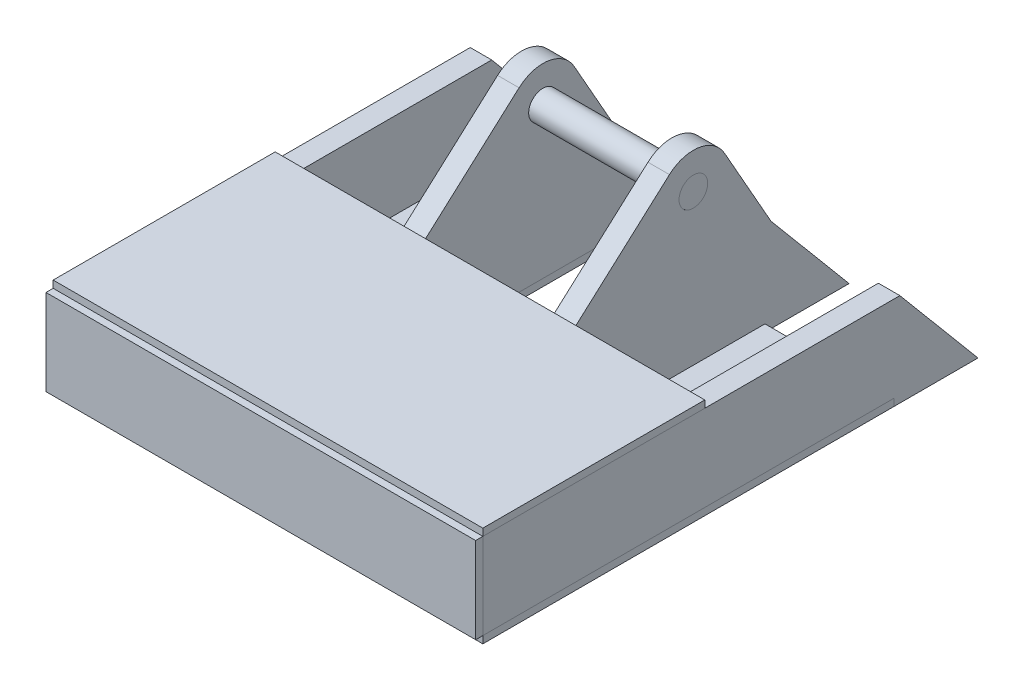
SolidWorks part; units mm, degrees
material "Alum Plate"
ref_plane "Front Plane" through (0, 0, 0) normal (0, 0, 1) x (1, 0, 0)
ref_plane "Top Plane" through (0, 0, 0) normal (0, 1, 0) x (1, 0, 0)
ref_plane "Right Plane" through (0, 0, 0) normal (1, 0, 0) x (0, 0, -1)
other "Bounding Box"
ref_plane "Default Plane" through (-8.9266, -12.7485, 0) normal (-0.1736, 0.9848, 0) x (0.9848, 0.1736, 0)
sketch "Sketch1" plane through (0, 0, 0) normal (0, 1, 0) x (1, 0, 0)
  line L0 (0, 0) -> (95.25, 0) construction
  line L1 (0, 0) -> (-95.25, 0) construction
  line L2 (-95.25, 139.7) -> (-146.05, 139.7) construction
  line L3 (95.25, 139.7) -> (146.05, 139.7) construction
  line L4 (0, 139.7) -> (0, 0) construction
  line L5 (-28.575, 131.445) -> (0, 131.445) construction
  line L6 (-95.25, 163.195) -> (95.25, 163.195) construction
  line L7 (-95.25, 163.195) -> (-95.25, -19.05) construction
  line L8 (-95.25, -19.05) -> (95.25, -19.05) construction
  line L9 (95.25, 163.195) -> (95.25, -19.05) construction
  line L10 (-78.105, 121.725) -> (-38.1, 121.725)
  line L11 (-78.105, 121.725) -> (-78.105, 157.725)
  line L12 (-78.105, 157.725) -> (-38.1, 157.725)
  line L13 (-38.1, 121.725) -> (-38.1, 157.725)
  line L14 (-78.105, 121.725) -> (-38.1, 157.725) construction
  line L15 (-78.105, 157.725) -> (-38.1, 121.725) construction
  line L16 (-78.105, 82.55) -> (-38.1, 82.55)
  line L17 (-78.105, 82.55) -> (-78.105, 118.55)
  line L18 (-78.105, 118.55) -> (-38.1, 118.55)
  line L19 (-38.1, 82.55) -> (-38.1, 118.55)
  line L20 (-78.105, 82.55) -> (-38.1, 118.55) construction
  line L21 (-78.105, 118.55) -> (-38.1, 82.55) construction
  line L22 (-38.1, 82.55) -> (-3.175, 82.55)
  line L23 (-38.1, 82.55) -> (-38.1, 118.55)
  line L24 (-38.1, 118.55) -> (-3.175, 118.55)
  line L25 (-3.175, 82.55) -> (-3.175, 118.55)
  line L26 (-38.1, 82.55) -> (-3.175, 118.55) construction
  line L27 (-38.1, 118.55) -> (-3.175, 82.55) construction
  line L28 (-28.575, 163.195) -> (-38.1, 163.195)
  line L29 (-28.575, 163.195) -> (-28.575, 79.375)
  line L30 (-28.575, 79.375) -> (-38.1, 79.375)
  line L31 (-38.1, 163.195) -> (-38.1, 79.375)
  line L32 (-28.575, 163.195) -> (-38.1, 79.375) construction
  line L33 (-28.575, 79.375) -> (-38.1, 163.195) construction
  line L34 (28.575, 163.195) -> (38.1, 163.195)
  line L35 (28.575, 163.195) -> (28.575, 79.375)
  line L36 (28.575, 79.375) -> (38.1, 79.375)
  line L37 (38.1, 163.195) -> (38.1, 79.375)
  line L38 (28.575, 163.195) -> (38.1, 79.375) construction
  line L39 (28.575, 79.375) -> (38.1, 163.195) construction
  line L40 (-95.25, 79.375) -> (95.25, 79.375)
  line L41 (-95.25, 79.375) -> (-95.25, 69.85)
  line L42 (-95.25, 69.85) -> (95.25, 69.85)
  line L43 (95.25, 79.375) -> (95.25, 69.85)
  line L44 (-95.25, 79.375) -> (95.25, 69.85) construction
  line L45 (-95.25, 69.85) -> (95.25, 79.375) construction
  line L46 (95.25, -19.05) -> (85.725, -19.05)
  line L47 (95.25, -19.05) -> (95.25, 163.195)
  line L48 (95.25, 163.195) -> (85.725, 163.195)
  line L49 (85.725, -19.05) -> (85.725, 163.195)
  line L50 (95.25, -19.05) -> (85.725, 163.195) construction
  line L51 (95.25, 163.195) -> (85.725, -19.05) construction
  line L52 (-95.25, -19.05) -> (-85.725, -19.05)
  line L53 (-95.25, -19.05) -> (-95.25, 163.195)
  line L54 (-95.25, 163.195) -> (-85.725, 163.195)
  line L55 (-85.725, -19.05) -> (-85.725, 163.195)
  line L56 (-95.25, -19.05) -> (-85.725, 163.195) construction
  line L57 (-95.25, 163.195) -> (-85.725, -19.05) construction
  line L58 (0, 131.445) -> (28.575, 131.445) construction
  line L59 (-95.25, 0) -> (-146.05, 0) construction
  line L60 (40.64, 82.55) -> (83.185, 82.55)
  line L61 (40.64, 82.55) -> (40.64, 160.02)
  line L62 (40.64, 160.02) -> (83.185, 160.02)
  line L63 (83.185, 82.55) -> (83.185, 160.02)
  line L64 (40.64, 82.55) -> (83.185, 160.02) construction
  line L65 (40.64, 160.02) -> (83.185, 82.55) construction
  line L66 (-95.25, -19.05) -> (95.25, -19.05)
  line L67 (-95.25, -19.05) -> (-95.25, -22.225)
  line L68 (-95.25, -22.225) -> (95.25, -22.225)
  line L69 (95.25, -19.05) -> (95.25, -22.225)
  line L70 (-95.25, -19.05) -> (95.25, -22.225) construction
  line L71 (-95.25, -22.225) -> (95.25, -19.05) construction
  line L72 (-85.725, -19.05) -> (-43.815, -19.05)
  line L73 (-85.725, -19.05) -> (-85.725, 19.05)
  line L74 (-85.725, 19.05) -> (-43.815, 19.05)
  line L75 (-43.815, -19.05) -> (-43.815, 19.05)
  line L76 (-85.725, -19.05) -> (-43.815, 19.05) construction
  line L77 (-85.725, 19.05) -> (-43.815, -19.05) construction
  line L78 (43.815, 19.05) -> (85.725, 19.05)
  line L79 (43.815, 19.05) -> (43.815, -19.05)
  line L80 (43.815, -19.05) -> (85.725, -19.05)
  line L81 (85.725, 19.05) -> (85.725, -19.05)
  line L82 (43.815, 19.05) -> (85.725, -19.05) construction
  line L83 (43.815, -19.05) -> (85.725, 19.05) construction
  line L84 (95.25, 0) -> (146.05, 0) construction
  line L85 (40.64, 121.285) -> (38.1, 121.285) construction
  line L86 (83.185, 121.285) -> (85.725, 121.285) construction
  line L88 (-8.89, -18) -> (-43.815, -18)
  line L89 (-8.89, -18) -> (-8.89, 18)
  line L90 (-8.89, 18) -> (-43.815, 18)
  line L91 (-43.815, -18) -> (-43.815, 18)
  line L92 (-8.89, -18) -> (-43.815, 18) construction
  line L93 (-8.89, 18) -> (-43.815, -18) construction
  line L94 (8.89, -18) -> (43.815, -18)
  line L95 (8.89, -18) -> (8.89, 18)
  line L96 (8.89, 18) -> (43.815, 18)
  line L97 (43.815, -18) -> (43.815, 18)
  line L98 (8.89, -18) -> (43.815, 18) construction
  line L99 (8.89, 18) -> (43.815, -18) construction
  point P15 (-58.1025, 100.55)
  point P23 (-58.1025, 139.725)
  point P26 (-20.6375, 100.55)
  point P30 (33.3375, 121.285)
  point P37 (-33.3375, 121.285)
  point P40 (0, 74.6125)
  point P43 (90.4875, 72.0725)
  point P46 (-90.4875, 72.0725)
  point P52 (0, -20.6375)
  point P54 (61.9125, 121.285)
  point P60 (64.77, 0)
  point P62 (-64.77, 0)
  point P71 (-26.3525, 0)
  point P78 (26.3525, 0)
  dimension "D1" = 36
  dimension "D2" = 47.625
  dimension "D3" = 3.175
  dimension "D4" = 34.925
  dimension "D5" = 40.005
  dimension "D6" = 38.1
  dimension "D7" = 9.525
  dimension "D8" = 9.525
  dimension "D9" = 42.545
  dimension "D10" = 77.47
  dimension "D11" = 3.175
  dimension "D12" = 3.175
  dimension "D13" = 3.175
  dimension "D14" = 38.1
  dimension "D15" = 41.91
  dimension "D16" = 139.7
  dimension "D17" = 3.175
  dimension "D18" = 50.8
  dimension "D19" = 88.9
  dimension "D20" = 9.525
  dimension "D21" = 36
  dimension "D22" = 34.925
  dimension "D23" = 31.75
sketch "Sketch2" plane through (0, 0, 0) normal (1, 0, 0) x (0, 0, -1)
  line L0 (-277.7757, 0) -> (556.0914, 0) construction
  line L1 (0, 31.75) -> (0, 0) construction
  line L2 (139.7, 0) -> (139.7, 31.75) construction
  line L3 (-19.05, 31.75) -> (0, 31.75) construction
  line L4 (-19.05, 12.7) -> (163.195, 12.7)
  line L5 (-19.05, 12.7) -> (-19.05, 50.8)
  line L6 (-19.05, 50.8) -> (163.195, 50.8)
  line L7 (163.195, 12.7) -> (163.195, 50.8)
  line L8 (-19.05, 12.7) -> (163.195, 50.8) construction
  line L9 (-19.05, 50.8) -> (163.195, 12.7) construction
  line L10 (0, 31.75) -> (139.7, 31.75) construction
  line L11 (139.7, 31.75) -> (163.195, 31.75) construction
  line L12 (131.445, 79.375) -> (131.445, 0) construction
  line L13 (-19.05, 12.7) -> (-22.225, 12.7)
  line L14 (-19.05, 12.7) -> (-19.05, 50.8)
  line L15 (-19.05, 50.8) -> (-22.225, 50.8)
  line L16 (-22.225, 12.7) -> (-22.225, 50.8)
  line L17 (-19.05, 12.7) -> (-22.225, 50.8) construction
  line L18 (-19.05, 50.8) -> (-22.225, 12.7) construction
  line L19 (79.375, 50.8) -> (69.85, 50.8)
  line L20 (79.375, 50.8) -> (79.375, 12.7)
  line L21 (79.375, 12.7) -> (69.85, 12.7)
  line L22 (69.85, 50.8) -> (69.85, 12.7)
  line L23 (79.375, 50.8) -> (69.85, 12.7) construction
  line L24 (79.375, 12.7) -> (69.85, 50.8) construction
  line L25 (-90.4552, 66.9109) -> (131.445, 79.375) construction
  line L26 (-22.225, 12.7) -> (163.195, 12.7)
  line L27 (-22.225, 12.7) -> (-22.225, 9.525)
  line L28 (-22.225, 9.525) -> (163.195, 9.525)
  line L29 (163.195, 12.7) -> (163.195, 9.525)
  line L30 (-22.225, 12.7) -> (163.195, 9.525) construction
  line L31 (-22.225, 9.525) -> (163.195, 12.7) construction
  line L32 (-22.225, 50.8) -> (163.195, 50.8)
  line L33 (-22.225, 50.8) -> (-22.225, 53.975)
  line L34 (-22.225, 53.975) -> (163.195, 53.975)
  line L35 (163.195, 50.8) -> (163.195, 53.975)
  line L36 (-22.225, 50.8) -> (163.195, 53.975) construction
  line L37 (-22.225, 53.975) -> (163.195, 50.8) construction
  line L40 (-90.7074, 85.9592) -> (131.3189, 88.8992)
  line L41 (132.3863, 69.8966) -> (-88.5727, 47.9542)
  line L42 (100.55, 39.0496) -> (131.445, 79.375) construction
  line L43 (131.445, 79.375) -> (139.725, 29.2543) construction
  line L45 (163.195, 53.975) -> (200.493, 9.525)
  line L46 (200.493, 9.525) -> (163.195, 9.525)
  circle A0 centre (0, 31.75) radius 31.75
  circle A2 centre (100.55, 39.0496) radius 18
  circle A3 centre (139.725, 29.2543) radius 18
  circle A4 centre (131.445, 79.375) radius 23.8125
  circle A5 centre (139.725, 29.2543) radius 12.7
  circle A6 centre (100.55, 39.0496) radius 9.525
  circle A7 centre (139.7, 25.4) radius 25.4
  circle A8 centre (-90.4552, 66.9109) radius 63.5
  circle A11 centre (-90.4552, 66.9109) radius 19.05
  circle A12 centre (131.445, 79.375) radius 9.525
  point P13 (-20.6375, 31.75)
  point P15 (72.0725, 31.75)
  point P21 (74.6125, 31.75)
  point P34 (82.55, 39.0496)
  point P35 (118.55, 39.0496)
  point P36 (121.725, 29.2543)
  point P37 (157.725, 29.2543)
  point P52 (70.485, 11.1125)
  point P54 (70.485, 52.3875)
  dimension "D1" = 63.5
  dimension "D3" = 19.05
  dimension "D4" = 25.4
  dimension "D5" = 47.625
  dimension "D8" = 50.8
  dimension "D9" = 127
  dimension "D10" = 38.1
  dimension "D2" = 38.1
  dimension "D6" = 3.175
  dimension "D7" = 3.175
  dimension "D11" = 222.25
  dimension "D12" = 25.4
  dimension "D13" = 50.8
  dimension "D14" = 50.8
  dimension "D15" = 50
sketch "Sketch3" plane through (0, 0, 0) normal (1, 0, 0) x (0, 0, -1)
  line L1 (69.85, 50.8) -> (79.375, 50.8)
  line L2 (69.85, 50.8) -> (69.85, 12.7)
  line L3 (69.85, 12.7) -> (79.375, 12.7)
  line L4 (79.375, 50.8) -> (79.375, 12.7)
  line L5 (69.85, 50.8) -> (79.375, 12.7) construction
  line L6 (69.85, 12.7) -> (79.375, 50.8) construction
  point P0 (74.6125, 31.75)
extrude "Boss-Extrude1" add sketch "Sketch3" along normal up to vertex (85.725 mm away) and the other way up to vertex (85.725 mm away) up to point (85.725, 0, 19.05) other way up to point (-85.725, 0, 19.05)
sketch "Sketch4" plane through (-85.725, 0, 0) normal (-1, 0, 0) x (0, 0, 1)
  line L0 (-200.493, 9.525) -> (-165.8591, 50.8)
  line L2 (-165.8591, 50.8) -> (19.05, 50.8)
  line L3 (19.05, 50.8) -> (19.05, 12.7)
  line L4 (19.05, 12.7) -> (-163.195, 12.7)
  line L5 (-163.195, 12.7) -> (-163.195, 9.525)
  line L6 (22.225, 12.7) -> (-163.195, 9.525) construction
  line L7 (22.225, 9.525) -> (-163.195, 9.525) construction
  line L8 (-163.195, 9.525) -> (-200.493, 9.525)
  line L10 (-163.195, 53.975) -> (-200.493, 9.525) construction
  point P4 (-165.8591, 50.8)
  point P5 (-165.8591, 50.8)
  point P18 (0, 0)
extrude "Boss-Extrude2" add sketch "Sketch4" along normal up to vertex (9.525 mm away) separate body up to point (-95.25, 0, 19.05)
ref_plane "Plane1" through (-38.1, 0, 0) normal (1, 0, 0) x (0, 0, -1)
sketch "Sketch5" plane through (-38.1, 0, 0) normal (1, 0, 0) x (0, 0, -1)
  line L0 (79.375, 12.7) -> (79.375, 53.975)
  line L1 (79.375, 12.7) -> (79.375, 50.8) construction
  line L4 (79.375, 53.975) -> (120.8418, 91.1897)
  line L5 (165.8591, 50.8) -> (145.2607, 87.1944)
  line L6 (-22.225, 53.975) -> (163.195, 53.975) construction
  line L7 (163.195, 9.525) -> (200.493, 9.525)
  line L8 (200.493, 9.525) -> (165.8591, 50.8)
  line L10 (165.8591, 50.8) -> (-19.05, 50.8)
  line L11 (-19.05, 50.8) -> (-19.05, 12.7)
  line L12 (-19.05, 12.7) -> (163.195, 12.7)
  line L13 (163.195, 12.7) -> (163.195, 9.525)
  line L14 (163.195, 9.525) -> (200.493, 9.525)
  line L15 (200.493, 9.525) -> (165.8591, 50.8)
  line L19 (79.375, 12.7) -> (163.195, 12.7)
  line L20 (163.195, 12.7) -> (163.195, 9.525)
  arc A0 (145.2607, 87.1944) -> (120.8418, 91.1897) centre (131.445, 79.375) ccw
  circle A1 centre (131.445, 79.375) radius 6.35
  point P14 (80.1921, 53.975)
  point P18 (0, 0)
  point P19 (79.375, 53.975)
  point P22 (84.9262, 50.8)
  dimension "D3" = 15.875
  dimension "D4" = 12.7
  dimension "D1" = 0
extrude "Boss-Extrude3" add sketch "Sketch5" along normal up to vertex (9.525 mm away) separate body up to point (-28.575, 0, -163.195)
sketch "Sketch7" plane through (0, 0, 19.05) normal (0, 0, 1) x (1, 0, 0)
  line L0 (-95.25, 12.7) -> (-85.725, 12.7) construction
  line L1 (95.25, 12.7) -> (-95.25, 12.7)
  line L2 (95.25, 12.7) -> (95.25, 50.8)
  line L3 (95.25, 50.8) -> (-95.25, 50.8)
  line L4 (-95.25, 12.7) -> (-95.25, 50.8)
  line L5 (95.25, 12.7) -> (-95.25, 50.8) construction
  line L6 (95.25, 50.8) -> (-95.25, 12.7) construction
  line L7 (-95.25, 12.7) -> (-95.25, 50.8) construction
  line L8 (0, -71.726) -> (0, 71.726) construction
  point P0 (0, 31.75)
  point P6 (-95.25, 12.7)
  point P11 (0, 0)
extrude "Boss-Extrude4" add sketch "Sketch7" along normal up to vertex (3.175 mm away) separate body up to point (-95.25, 0, 22.225)
mirror "Mirror1" about plane through (0, 0, 0) normal (1, 0, 0) of bodies 106 105
sketch "Sketch8" plane through (0, 50.8, 0) normal (0, 1, 0) x (1, 0, 0)
  line L0 (-95.25, 79.375) -> (95.25, 79.375)
  line L5 (95.25, 79.375) -> (95.25, -19.05)
  line L6 (95.25, -19.05) -> (95.25, 165.8591) construction
  line L7 (95.25, -19.05) -> (-95.25, -19.05)
  line L8 (-95.25, -19.05) -> (-95.25, 79.375)
  point P1 (95.25, 79.375)
  point P4 (-28.575, 88.9)
  point P5 (93.7154, 88.9)
  point P19 (28.575, 88.9)
extrude "Boss-Extrude5" add sketch "Sketch8" along normal up to vertex (3.175 mm away) separate body up to point (0, 53.975, -163.195)
sketch "Sketch9" plane through (0, 12.7, 0) normal (0, -1, 0) x (1, 0, 0)
  line L0 (-95.25, -163.195) -> (-28.575, -163.195)
  line L1 (-28.575, -163.195) -> (-28.575, -79.375)
  line L2 (-28.575, -79.375) -> (28.575, -79.375)
  line L3 (28.575, -79.375) -> (28.575, -163.195)
  line L4 (28.575, -163.195) -> (95.25, -163.195)
  line L5 (95.25, -163.195) -> (95.25, 19.05)
  line L6 (95.25, 19.05) -> (-95.25, 19.05)
  line L7 (-95.25, 19.05) -> (-95.25, -163.195)
extrude "Boss-Extrude6" add sketch "Sketch9" along normal up to vertex (3.175 mm away) separate body up to point (0, 9.525, 22.225)
sketch "Sketch10" plane through (-38.1, 0, 0) normal (-1, 0, 0) x (0, 0, 1)
  circle A0 centre (-131.445, 79.375) radius 6.35 construction
  circle A1 centre (-131.445, 79.375) radius 6.35
extrude "Boss-Extrude7" add sketch "Sketch10" against normal up to surface (76.2 mm away) separate body up to face at (38.1, 41.6823, -139.819)
ref_plane "Plane2" through (0, 0, -19.05) normal (0, 0, -1) x (-1, 0, 0)
sketch "Sketch11" plane through (0, 0, -19.05) normal (0, 0, -1) x (-1, 0, 0)
  line L1 (-85.725, 12.7) -> (85.725, 12.7)
  line L2 (-85.725, 12.7) -> (-85.725, 50.8)
  line L3 (-85.725, 50.8) -> (85.725, 50.8)
  line L4 (85.725, 12.7) -> (85.725, 50.8)
  line L5 (-85.725, 12.7) -> (85.725, 50.8) construction
  line L6 (-85.725, 50.8) -> (85.725, 12.7) construction
  point P4 (0, 31.75)
  point P5 (0, 0)
extrude "Boss-Extrude8" add sketch "Sketch11" along normal blind 1.6002 separate body
